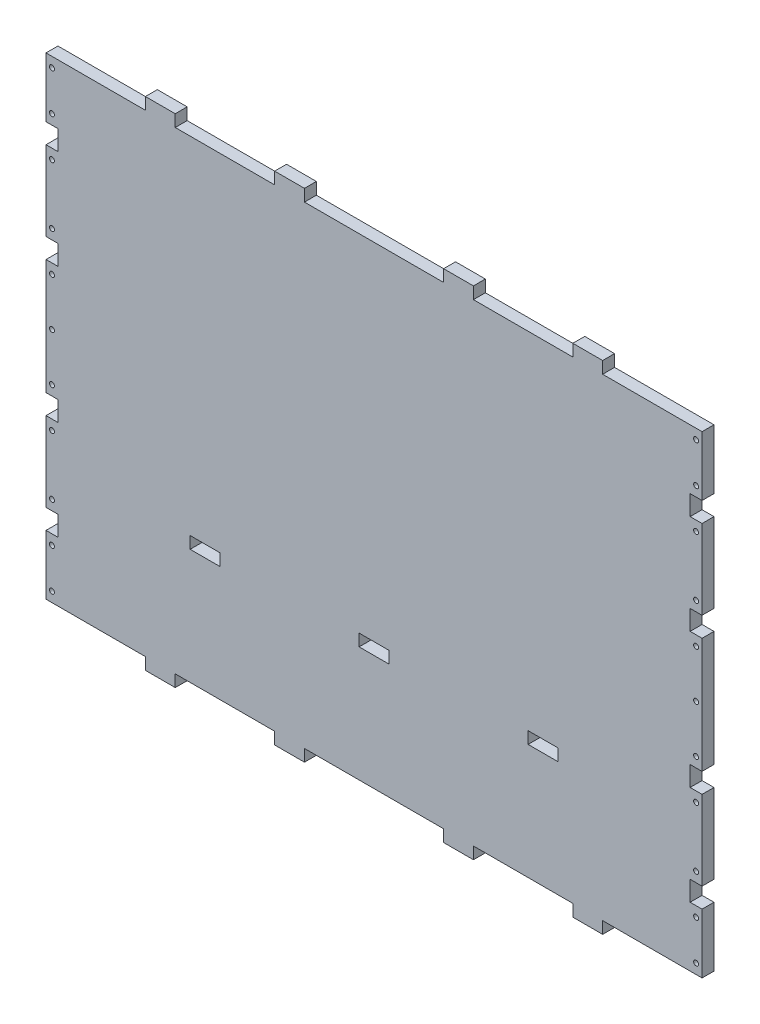
SolidWorks part; units mm, degrees
ref_plane "Plan de face" through (0, 0, 0) normal (0, 0, 1) x (1, 0, 0)
ref_plane "Plan de dessus" through (0, 0, 0) normal (0, 1, 0) x (1, 0, 0)
ref_plane "Plan de droite" through (0, 0, 0) normal (1, 0, 0) x (0, 0, -1)
sketch "Esquisse1" plane through (0, 0, 0) normal (0, 0, 1) x (1, 0, 0)
  line L0 (97.3951, 0) -> (-118.5049, 0) construction
  line L1 (-165, 119) -> (165, 119)
  line L2 (-165, 119) -> (-165, -119)
  line L3 (-165, -119) -> (165, -119)
  line L4 (165, 119) -> (165, -119)
  line L5 (0, 79.3588) -> (0, -79.3588) construction
  line L6 (-92.5, -55) -> (-77.5, -55)
  line L7 (-92.5, -55) -> (-92.5, -61)
  line L8 (-92.5, -61) -> (-77.5, -61)
  line L9 (-77.5, -55) -> (-77.5, -61)
  line L10 (-7.5, -55) -> (7.5, -55)
  line L11 (-7.5, -55) -> (-7.5, -61)
  line L12 (-7.5, -61) -> (7.5, -61)
  line L13 (7.5, -55) -> (7.5, -61)
  line L14 (77.5, -55) -> (92.5, -55)
  line L15 (77.5, -55) -> (77.5, -61)
  line L16 (77.5, -61) -> (92.5, -61)
  line L17 (92.5, -55) -> (92.5, -61)
  dimension "D1" = 238
  dimension "D2" = 330
  dimension "D3" = 165
  dimension "D4" = 119
  dimension "D5" = 15
  dimension "D6" = 6
  dimension "D7" = 6
  dimension "D8" = 15
  dimension "D9" = 6
  dimension "D10" = 15
  dimension "D11" = 70
  dimension "D12" = 70
  dimension "D13" = 58
  dimension "D14" = 72.5
extrude "Boss.-Extru.1" add sketch "Esquisse1" along normal blind 6
sketch "Esquisse2" plane through (0, 0, 6) normal (0, 0, 1) x (1, 0, 0)
  line L0 (243.146, 0) -> (-260.0003, 0) construction
  line L1 (0, 180.4713) -> (0, -129.6072) construction
  line L2 (165, 119) -> (-165, 119) construction
  line L3 (-115, 119) -> (-100, 119)
  line L4 (-115, 119) -> (-115, 125)
  line L5 (-115, 125) -> (-100, 125)
  line L6 (-100, 119) -> (-100, 125)
  line L7 (-165, 119) -> (-165, -119) construction
  line L8 (-50, 119) -> (-35, 119)
  line L9 (-50, 119) -> (-50, 125)
  line L10 (-50, 125) -> (-35, 125)
  line L11 (-35, 119) -> (-35, 125)
  line L12 (35, 119) -> (35, 125)
  line L13 (50, 125) -> (35, 125)
  line L14 (50, 119) -> (50, 125)
  line L15 (50, 119) -> (35, 119)
  line L16 (100, 119) -> (100, 125)
  line L17 (115, 125) -> (100, 125)
  line L18 (115, 119) -> (115, 125)
  line L19 (115, 119) -> (100, 119)
  line L20 (-115, 119) -> (-100, 119)
  line L21 (-115, 119) -> (-115, 125)
  line L22 (-115, 125) -> (-100, 125)
  line L23 (-100, 119) -> (-100, 125)
  line L24 (-50, 119) -> (-35, 119)
  line L25 (-50, 119) -> (-50, 125)
  line L26 (-50, 125) -> (-35, 125)
  line L27 (-35, 119) -> (-35, 125)
  line L28 (35, 119) -> (35, 125)
  line L29 (50, 125) -> (35, 125)
  line L30 (50, 119) -> (50, 125)
  line L31 (50, 119) -> (35, 119)
  line L32 (100, 119) -> (100, 125)
  line L33 (115, 125) -> (100, 125)
  line L34 (115, 119) -> (115, 125)
  line L35 (115, 119) -> (100, 119)
  line L36 (115, -119) -> (100, -119)
  line L37 (115, -119) -> (115, -125)
  line L38 (115, -125) -> (100, -125)
  line L39 (100, -119) -> (100, -125)
  line L40 (50, -119) -> (35, -119)
  line L41 (50, -119) -> (50, -125)
  line L42 (50, -125) -> (35, -125)
  line L43 (35, -119) -> (35, -125)
  line L44 (-35, -119) -> (-35, -125)
  line L45 (-50, -125) -> (-35, -125)
  line L46 (-50, -119) -> (-50, -125)
  line L47 (-50, -119) -> (-35, -119)
  line L48 (-100, -119) -> (-100, -125)
  line L49 (-115, -125) -> (-100, -125)
  line L50 (-115, -119) -> (-115, -125)
  line L51 (-115, -119) -> (-100, -119)
  line L52 (115, -119) -> (100, -119)
  line L53 (115, -119) -> (115, -125)
  line L54 (115, -125) -> (100, -125)
  line L55 (100, -119) -> (100, -125)
  line L56 (50, -119) -> (35, -119)
  line L57 (50, -119) -> (50, -125)
  line L58 (50, -125) -> (35, -125)
  line L59 (35, -119) -> (35, -125)
  line L60 (-35, -119) -> (-35, -125)
  line L61 (-50, -125) -> (-35, -125)
  line L62 (-50, -119) -> (-50, -125)
  line L63 (-50, -119) -> (-35, -119)
  line L64 (-100, -119) -> (-100, -125)
  line L65 (-115, -125) -> (-100, -125)
  line L66 (-115, -119) -> (-115, -125)
  line L67 (-115, -119) -> (-100, -119)
  line M9 (-165, -119) -> (165, -119)
  line M11 (165, 119) -> (-165, 119)
  dimension "D1" = 6
  dimension "D2" = 6
  dimension "D3" = 15
  dimension "D4" = 15
  dimension "D5" = 50
  dimension "D6" = 50
extrude "Boss.-Extru.2" add sketch "Esquisse2" against normal blind 6 contours L6 L5 L4 M11 | L11 L10 L9 M11 | L14 L13 L12 M11 | L18 L17 L16 M11 | L39 L38 L37 M9 | L43 L42 L41 M9 | L46 L45 L44 M9 | L50 L49 L48 M9 region at (-107.5, 122, 6) region at (107.5, 122, 6) region at (42.5, 122, 6) region at (-42.5, 122, 6) region at (107.5, -122, 6) region at (-107.5, -122, 6) region at (-42.5, -122, 6) region at (42.5, -122, 6)
sketch "Esquisse3" plane through (0, 0, 6) normal (0, 0, 1) x (1, 0, 0)
  line L0 (-165, 119) -> (-165, -119) construction
  line L1 (-165, 79) -> (-159, 79)
  line L2 (-165, 79) -> (-165, 89)
  line L3 (-165, 89) -> (-159, 89)
  line L4 (-159, 79) -> (-159, 89)
  line L5 (234.1368, 0) -> (-337.9213, 0) construction
  line L6 (-165, 39) -> (-159, 39)
  line L7 (-165, 39) -> (-165, 29)
  line L8 (-165, 29) -> (-159, 29)
  line L9 (-159, 39) -> (-159, 29)
  line L10 (0, 279.7488) -> (0, -188.1201) construction
  line L11 (-115, 119) -> (-165, 119) construction
  line L12 (-159, -39) -> (-159, -29)
  line L13 (-165, -29) -> (-159, -29)
  line L14 (-165, -39) -> (-165, -29)
  line L15 (-165, -39) -> (-159, -39)
  line L16 (-159, -79) -> (-159, -89)
  line L17 (-165, -89) -> (-159, -89)
  line L18 (-165, -79) -> (-165, -89)
  line L19 (-165, -79) -> (-159, -79)
  line L20 (165, -79) -> (159, -79)
  line L21 (165, -79) -> (165, -89)
  line L22 (165, -89) -> (159, -89)
  line L23 (159, -79) -> (159, -89)
  line L24 (165, -39) -> (159, -39)
  line L25 (165, -39) -> (165, -29)
  line L26 (165, -29) -> (159, -29)
  line L27 (159, -39) -> (159, -29)
  line L28 (159, 39) -> (159, 29)
  line L29 (165, 29) -> (159, 29)
  line L30 (165, 39) -> (165, 29)
  line L31 (165, 39) -> (159, 39)
  line L32 (159, 79) -> (159, 89)
  line L33 (165, 89) -> (159, 89)
  line L34 (165, 79) -> (165, 89)
  line L35 (165, 79) -> (159, 79)
  dimension "D1" = 40
  dimension "D2" = 6
  dimension "D3" = 6
  dimension "D4" = 10
  dimension "D5" = 10
  dimension "D6" = 30
extrude "Enlèv. mat.-Extru.1" cut sketch "Esquisse3" against normal blind 6
sketch "Esquisse4" plane through (0, 0, 6) normal (0, 0, 1) x (1, 0, 0)
  line L0 (-162, 121.7279) -> (-162, -131.0602) construction
  line L1 (0, 158.5579) -> (0, -182.4489) construction
  line L2 (-115, 119) -> (-165, 119) construction
  line L4 (-159, 89) -> (-165, 89) construction
  line L5 (-165, 119) -> (-165, 89) construction
  line L6 (-165, 79) -> (-159, 79) construction
  line L7 (-159, 39) -> (-165, 39) construction
  line L8 (-165, 29) -> (-159, 29) construction
  line L9 (-159, -29) -> (-165, -29) construction
  line L12 (-165, -39) -> (-159, -39) construction
  line L13 (-159, -79) -> (-165, -79) construction
  line L14 (-165, -89) -> (-159, -89) construction
  line L15 (-165, -119) -> (-115, -119) construction
  line L16 (162, 121.7279) -> (162, -131.0602) construction
  circle A0 centre (-162, 114) radius 1.25
  circle A1 centre (-162, 94) radius 1.25
  circle A2 centre (-162, 74) radius 1.25
  circle A3 centre (-162, 44) radius 1.25
  circle A4 centre (-162, 24) radius 1.25
  circle A5 centre (-162, 0) radius 1.25
  circle A6 centre (-162, -24) radius 1.25
  circle A7 centre (-162, -44) radius 1.25
  circle A8 centre (-162, -74) radius 1.25
  circle A9 centre (-162, -94) radius 1.25
  circle A10 centre (-162, -114) radius 1.25
  circle A11 centre (162, -114) radius 1.25
  circle A12 centre (162, -94) radius 1.25
  circle A13 centre (162, -74) radius 1.25
  circle A14 centre (162, -44) radius 1.25
  circle A15 centre (162, -24) radius 1.25
  circle A16 centre (162, 0) radius 1.25
  circle A17 centre (162, 24) radius 1.25
  circle A18 centre (162, 44) radius 1.25
  circle A19 centre (162, 74) radius 1.25
  circle A20 centre (162, 94) radius 1.25
  circle A21 centre (162, 114) radius 1.25
  dimension "D1" = 2.5
  dimension "D2" = 2.5
  dimension "D3" = 2.5
  dimension "D4" = 2.5
  dimension "D5" = 2.5
  dimension "D6" = 2.5
  dimension "D7" = 2.5
  dimension "D8" = 2.5
  dimension "D9" = 2.5
  dimension "D10" = 2.5
  dimension "D11" = 2.5
  dimension "D12" = 5
  dimension "D13" = 5
  dimension "D15" = 5
  dimension "D16" = 5
  dimension "D17" = 5
  dimension "D19" = 29
  dimension "D20" = 5
  dimension "D21" = 5
  dimension "D23" = 5
  dimension "D14" = 3
  dimension "D18" = 5
  dimension "D22" = 5
extrude "Enlèv. mat.-Extru.2" cut sketch "Esquisse4" against normal blind 6
equation "\"D3@Esquisse1\"=\"D2@Esquisse1\"/2"
equation "\"D4@Esquisse1\"=\"D1@Esquisse1\"/2"
